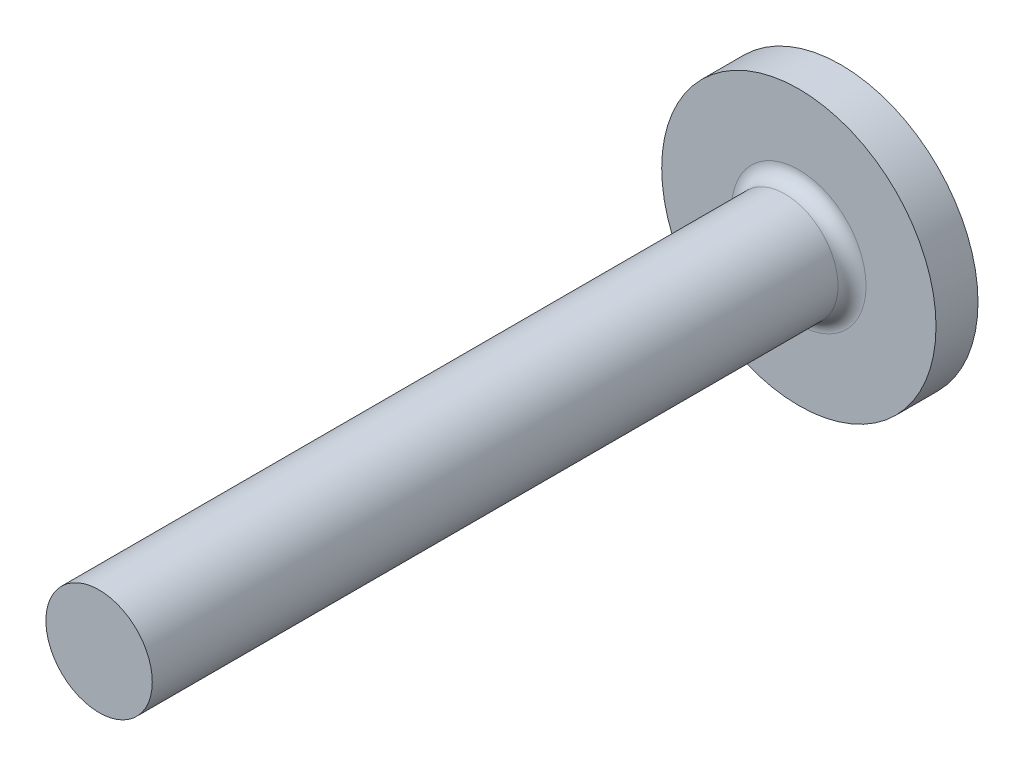
SolidWorks part; units mm, degrees
ref_plane "Front Plane" through (0, 0, 0) normal (0, 0, 1) x (1, 0, 0)
ref_plane "Top Plane" through (0, 0, 0) normal (0, 1, 0) x (1, 0, 0)
ref_plane "Right Plane" through (0, 0, 0) normal (1, 0, 0) x (0, 0, -1)
sketch "Sketch1" plane through (0, 0, 0) normal (0, 0, 1) x (1, 0, 0)
  circle A0 centre (0, 0) radius 3.8
  circle A1 centre (0, 0) radius 9.8
  dimension "D1" = 7.6
  dimension "D2" = 6
extrude "Boss-Extrude1" add sketch "Sketch1" along normal blind 50 contours A0 region at (0, 0, 0)
extrude "Boss-Extrude2" add sketch "Sketch1<3>" against normal blind 3 contours A1 A0 | A0 region at (0, 0, 0) region at (-9.5228, 0, 0)
sketch "Sketch1<3>" plane through (0, 0, 0) normal (0, 0, 1) x (1, 0, 0) same geometry as "Sketch1"
fillet "Fillet1" radius 1 1 edges at (3.8, 0, 0)
